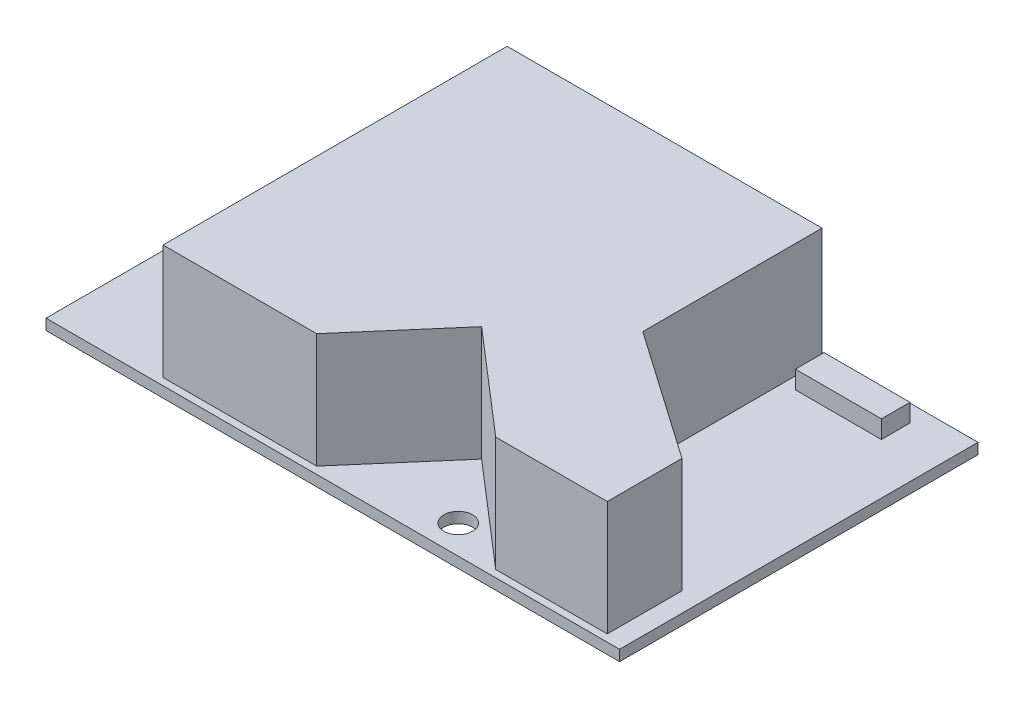
SolidWorks part; units mm, degrees
ref_plane "Front Plane" through (0, 0, 0) normal (0, 0, 1) x (1, 0, 0)
ref_plane "Top Plane" through (0, 0, 0) normal (0, 1, 0) x (1, 0, 0)
ref_plane "Right Plane" through (0, 0, 0) normal (1, 0, 0) x (0, 0, -1)
sketch "Sketch2" plane through (0, 0, 0) normal (0, 1, 0) x (1, 0, 0)
  line L0 (61.7293, -49) -> (47.4073, -36.6462)
  line L1 (0, 0) -> (80, 0)
  line L2 (0, 0) -> (0, -50)
  line L3 (0, -50) -> (80, -50)
  line L4 (80, 0) -> (80, -50)
  line L5 (15.3221, -1) -> (72.2939, -1)
  line L6 (15.3221, -1) -> (15.3221, -49)
  line L7 (15.3221, -49) -> (77.2927, -49)
  line L8 (77.2927, -1) -> (77.2927, -49)
  line L9 (47.4073, -36.6462) -> (36.7512, -49)
  line L10 (77.2927, -38.5831) -> (59.2465, -26)
  line L11 (59.2465, -26) -> (59.2465, -1)
  line L12 (59.2465, -1) -> (77.2927, -1)
  line L13 (77.2927, -38.5831) -> (77.2927, -1)
  line L14 (73.4043, -1) -> (61.4043, -1)
  line L15 (73.4043, -1) -> (61.4043, -1)
  line L20 (72.2939, -1) -> (60.2939, -1)
  line L24 (72.9239, -2.3978) -> (60.9239, -2.3978)
  line L25 (72.9239, -2.3978) -> (72.9239, -6.3978)
  line L26 (72.9239, -6.3978) -> (60.9239, -6.3978)
  line L27 (60.9239, -2.3978) -> (60.9239, -6.3978)
  circle A6 centre (53.5, -46) radius 2
  dimension "D3" = 4
  dimension "D6" = 26.5
  dimension "D12" = 25
  dimension "D13" = 12
  dimension "D14" = 4
  dimension "D16" = 2.3978
  dimension "D4" = 12.3538
  dimension "D7" = 4
  dimension "D1" = 80
  dimension "D2" = 50
  dimension "D5" = 14.3219
  dimension "D8" = 61.9706
  dimension "D9" = 48
  dimension "D10" = 1
  dimension "D11" = 22
  dimension "D15" = 60.9239
extrude "Boss-Extrude1" add sketch "Sketch2" along normal blind 1.5 contours L6 L5 L8 L7 | L2 L1 L4 L3 | A6
extrude "Boss-Extrude2" add sketch "Sketch2<3>" along normal blind 17.5 contours L8 L5 L6 L7 region at (40.4989, 0, 25.6787)
sketch "Sketch2<3>" plane through (0, 0, 0) normal (0, 1, 0) x (1, 0, 0) same geometry as "Sketch2"
extrude "Boss-Extrude3" add sketch "Sketch2<5>" along normal blind 4 contours L24 L27 L26 L25
sketch "Sketch2<5>" plane through (0, 0, 0) normal (0, 1, 0) x (1, 0, 0) same geometry as "Sketch2"
